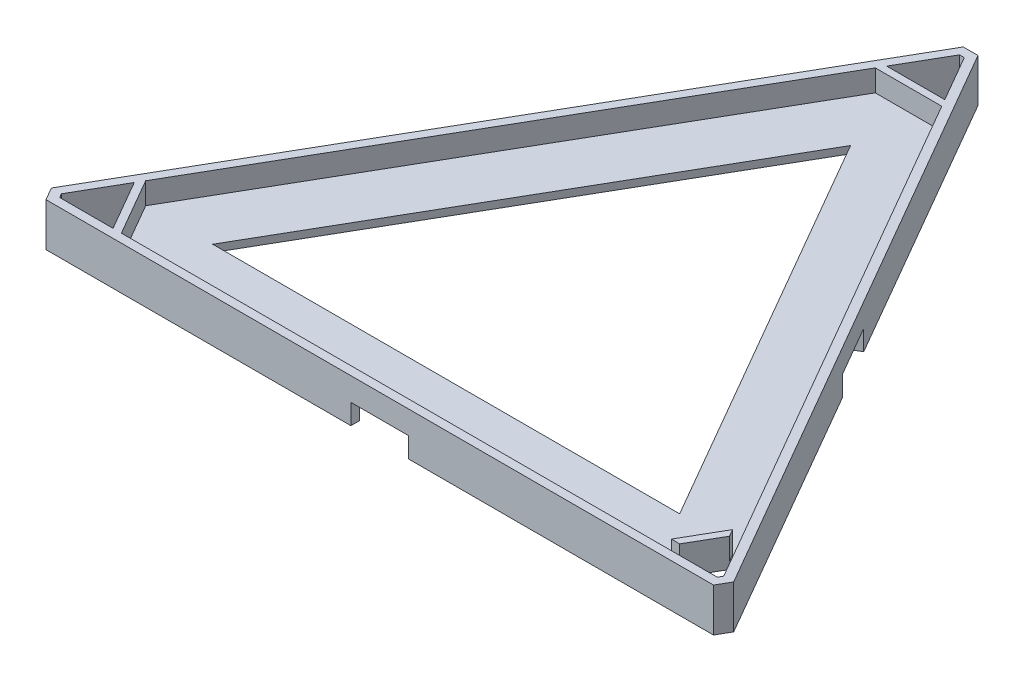
SolidWorks part; units mm, degrees
ref_plane "Front Plane" through (0, 0, 0) normal (0, 0, 1) x (1, 0, 0)
ref_plane "Top Plane" through (0, 0, 0) normal (0, 1, 0) x (1, 0, 0)
ref_plane "Right Plane" through (0, 0, 0) normal (1, 0, 0) x (0, 0, -1)
sketch "Sketch1" plane through (0, 0, 0) normal (0, 1, 0) x (1, 0, 0)
  line L0 (351.2729, 67.6655) -> (468.273, -134.9846)
  line L1 (347.2728, 67.6655) -> (347.2728, 65.1655) construction
  line L2 (409.773, -33.6595) -> (407.6079, -34.9095) construction
  line L3 (468.273, -134.9846) -> (464.2732, -141.9124)
  line L4 (230.2733, -141.9124) -> (464.2732, -141.9124)
  line L5 (230.2733, -141.9124) -> (226.2727, -134.9842)
  line L6 (226.2727, -134.9842) -> (343.2728, 67.6655)
  line L7 (353.4142, 63.9567) -> (351.2491, 62.7067) construction
  line L8 (347.2733, -141.9124) -> (347.2733, -139.4124) construction
  line L9 (231.7167, -139.4124) -> (462.8299, -139.4124)
  line L10 (284.7727, -33.6594) -> (286.9378, -34.9094) construction
  line L11 (344.7161, 65.1655) -> (349.8295, 65.1655)
  line L12 (465.3862, -134.9846) -> (349.8295, 65.1655)
  line L13 (466.2731, -138.4485) -> (464.1081, -137.1985) construction
  line L14 (462.8299, -139.4124) -> (465.3862, -134.9846)
  line L15 (229.1594, -134.9842) -> (344.7161, 65.1655)
  line L16 (229.1594, -134.9842) -> (231.7167, -139.4124)
  line L17 (286.9378, -34.9094) -> (287.3708, -35.1594) construction
  line L18 (230.438, -137.1983) -> (230.871, -136.9483) construction
  line L19 (232.0053, -138.9123) -> (229.7368, -134.9842)
  line L20 (343.2728, 67.6655) -> (351.2729, 67.6655)
  line L21 (345.0048, 64.6655) -> (229.7368, -134.9842)
  line L22 (349.5409, 64.6655) -> (345.0048, 64.6655)
  line L23 (249.0568, -126.4468) -> (246.8918, -127.697) construction
  line L24 (407.6079, -34.9095) -> (407.1749, -35.1595) construction
  line L26 (233.4463, -136.4089) -> (251.9226, -136.4093)
  line L27 (464.8089, -134.9846) -> (462.5412, -138.9123)
  line L28 (462.5412, -138.9123) -> (232.0053, -138.9123)
  line L29 (251.9226, -136.4093) -> (241.8609, -118.9847)
  line L30 (241.8609, -118.9847) -> (232.6236, -134.9842)
  line L31 (232.6236, -134.9842) -> (233.4463, -136.4089)
  line L33 (287.3708, -35.1594) -> (289.5359, -36.4094) construction
  line L34 (254.8093, -136.4089) -> (243.3042, -116.4848)
  line L35 (335.7675, 43.666) -> (243.3042, -116.4848)
  line L36 (358.7782, 43.666) -> (335.7675, 43.666)
  line L38 (289.5359, -36.4094) -> (306.8564, -46.4094) construction
  line L41 (461.939, -134.9846) -> (461.1164, -136.4093)
  line L42 (347.2688, -136.4172) -> (347.2688, -116.4172) construction
  line L43 (442.6021, -136.4093) -> (452.6999, -118.9847)
  line L44 (245.2636, -119.878) -> (249.0568, -126.4468) construction
  line L45 (452.6999, -118.9847) -> (461.939, -134.9846)
  line L48 (461.1164, -136.4093) -> (442.6021, -136.4093)
  line L49 (405.0134, -36.4027) -> (387.6936, -46.404) construction
  line L50 (306.8564, -46.4094) -> (466.2731, -138.4485) construction
  line L51 (357.3348, 46.166) -> (337.2109, 46.166)
  line L52 (337.2109, 46.166) -> (346.4484, 62.1659)
  line L53 (346.4484, 62.1659) -> (348.0966, 62.164)
  line L54 (348.0966, 62.164) -> (357.3348, 46.166)
  line L55 (228.273, -138.4483) -> (387.6936, -46.404) construction
  line L56 (347.2688, -116.4172) -> (347.2728, 43.666) construction
  line L57 (266.4391, -116.428) -> (428.1137, -116.4172)
  line L58 (347.2736, 23.6092) -> (428.1137, -116.4172)
  line L59 (266.4391, -116.428) -> (347.2736, 23.6092)
  line L60 (439.7283, -136.4254) -> (439.7283, -132.9254) construction
  line L61 (451.2487, -116.4715) -> (448.6507, -117.9717) construction
  line L62 (452.6999, -118.9847) -> (358.7782, 43.666)
  line L63 (442.6021, -136.4093) -> (254.8093, -136.4089)
  line L64 (441.749, -132.9254) -> (444.621, -132.9254)
  line L65 (448.6507, -117.9717) -> (450.9647, -121.979) construction
  line L66 (449.5167, -119.4714) -> (450.9647, -121.979)
  line L67 (441.749, -132.9254) -> (449.5167, -119.4714)
  line L68 (450.9647, -121.979) -> (444.621, -132.9254)
  point P13 (407.6079, -34.9095)
  point P20 (464.1081, -137.1985)
  point P23 (347.2733, -139.4124)
  point P25 (347.2732, -141.9124)
  point P27 (347.2728, 65.1655)
  point P31 (286.9378, -34.9094)
  point P37 (287.3708, -35.1594)
  point P39 (230.871, -136.9483)
  point P41 (347.2728, 64.6655)
  point P45 (407.1749, -35.1595)
  point P50 (246.8918, -127.697)
  point P56 (289.5359, -36.4094)
  point P58 (249.0568, -126.4468)
  point P60 (347.2728, 43.666)
  point P62 (345.0048, -136.4089)
  point P64 (445.4885, -126.4485)
  point P71 (447.651, -127.697)
  point P77 (347.2728, 46.166)
  point P84 (347.2688, -116.4172)
  point P87 (387.6936, -46.404)
  point P89 (306.8564, -46.4094)
  point P100 (405.0134, -36.4027)
  dimension "D1" = 2.5
  dimension "D2" = 2.5
  dimension "D3" = 2.5
  dimension "D4" = 2.5
  dimension "D5" = 2.5
  dimension "D6" = 2.5
  dimension "D7" = 0.5
  dimension "D8" = 0.5
  dimension "D9" = 0.5
  dimension "D10" = 2.5
  dimension "D11" = 2.5
  dimension "D12" = 20
  dimension "D13" = 20
  dimension "D14" = 20
  dimension "D15" = 3.5
  dimension "D16" = 3
extrude "Boss-Extrude1" add sketch "Sketch1" along normal blind 2.5 contours L36 L35 L34 L57 L59 L58 region at (251.4484, 0, 125.0658)
extrude "Boss-Extrude2" add sketch "Sketch1<9>" along normal blind 10 contours L28 L27 L22 L21 L19 L31 L30 L29 L26 L34 L35 L36 L41 L48 L43 L45 L53 L54 L51 L52 | L68 L64 L67 L66 region at (230.7087, 0, 137.042)
sketch "Sketch1<9>" plane through (0, 0, 0) normal (0, 1, 0) x (1, 0, 0) same geometry as "Sketch1"
extrude "Boss-Extrude3" add sketch "Sketch1<10>" along normal blind 10 and the other way blind 5 contours L28 L27 L22 L21 L19 L31 L30 L29 L26 L34 L35 L36 L41 L48 L43 L45 L53 L54 L51 L52 region at (230.7087, 0, 137.042)
sketch "Sketch1<10>" plane through (0, 0, 0) normal (0, 1, 0) x (1, 0, 0) same geometry as "Sketch1"
sketch "Sketch3" plane through (290.5896, 0, -167.772) normal (0.866, 0, -0.5) x (-0.5, 0, -0.866)
  line L1 (-246.593, -12) -> (-226.593, -12)
  line L2 (-246.593, -12) -> (-246.593, 2)
  line L3 (-246.593, 2) -> (-226.593, 2)
  line L4 (-226.593, -12) -> (-226.593, 2)
  line L5 (-246.593, -12) -> (-226.593, 2) construction
  line L6 (-246.593, 2) -> (-226.593, -12) construction
  point P0 (-236.593, -5)
  dimension "D1" = 20
  dimension "D2" = 14
extrude "Cut-Extrude3" cut sketch "Sketch3" against normal blind 20
sketch "Sketch5" plane through (0, 0, 139.4124) normal (0, 0, 1) x (1, 0, 0)
  line L0 (231.7167, -5) -> (462.8299, -5) construction
  line L1 (337.2733, -12) -> (357.2733, -12)
  line L2 (337.2733, -12) -> (337.2733, 2)
  line L3 (337.2733, 2) -> (357.2733, 2)
  line L4 (357.2733, -12) -> (357.2733, 2)
  line L5 (337.2733, -12) -> (357.2733, 2) construction
  line L6 (337.2733, 2) -> (357.2733, -12) construction
  point P0 (347.2733, -5)
  dimension "D1" = 20
  dimension "D2" = 14
extrude "Cut-Extrude4" cut sketch "Sketch5" against normal blind 20
sketch "Sketch6" plane through (230.3194, 0, 132.9752) normal (-0.866, 0, -0.5) x (-0.5, 0, 0.866)
  line L0 (2.3199, -5) -> (-228.7932, -5) construction
  line L1 (-123.2367, -12) -> (-103.2367, -12)
  line L2 (-123.2367, -12) -> (-123.2367, 2)
  line L3 (-123.2367, 2) -> (-103.2367, 2)
  line L4 (-103.2367, -12) -> (-103.2367, 2)
  line L5 (-123.2367, -12) -> (-103.2367, 2) construction
  line L6 (-123.2367, 2) -> (-103.2367, -12) construction
  point P0 (-113.2367, -5)
  dimension "D1" = 20
  dimension "D2" = 14
extrude "Cut-Extrude5" cut sketch "Sketch6" against normal blind 20
